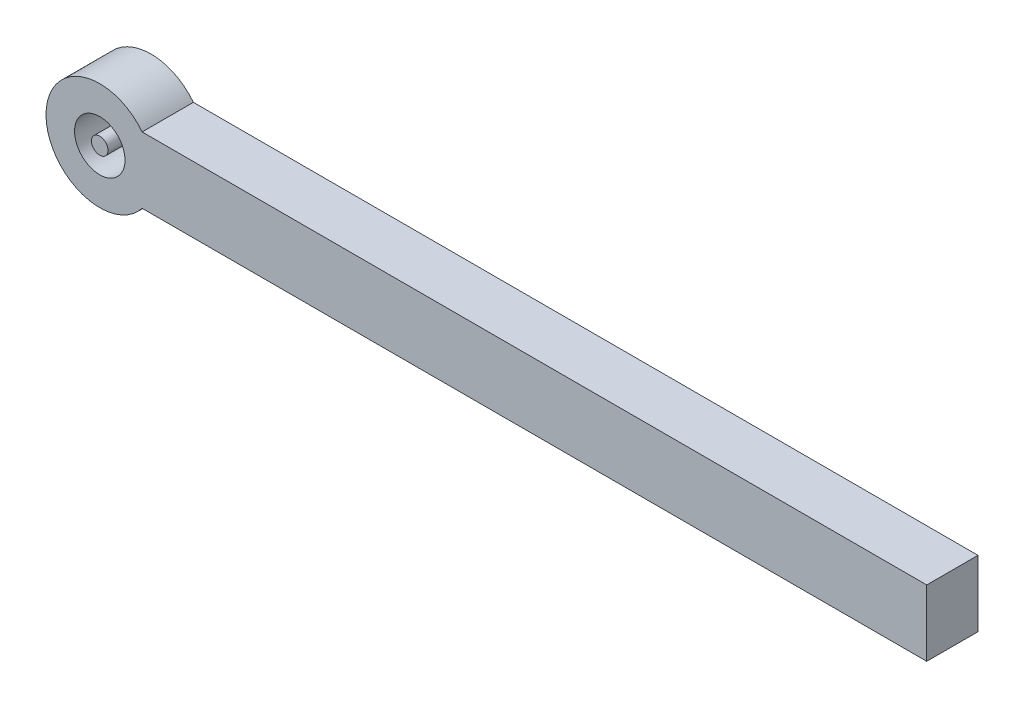
SolidWorks part; units mm, degrees
material "3d打印 35%"
ref_plane "前视基准面" through (0, 0, 0) normal (0, 0, 1) x (1, 0, 0)
ref_plane "上视基准面" through (0, 0, 0) normal (0, 1, 0) x (1, 0, 0)
ref_plane "右视基准面" through (0, 0, 0) normal (1, 0, 0) x (0, 0, -1)
other "Configuration Table"
sketch "草图1" plane through (0, 0, 0) normal (0, 0, 1) x (1, 0, 0)
  line L0 (0, 0) -> (0, 4) construction
  line L1 (0, 0) -> (0, -4) construction
  line L2 (5.1235, 4) -> (100, 4)
  line L3 (100, 4) -> (100, -4)
  line L4 (100, -4) -> (5.1235, -4)
  circle A0 centre (0, 0) radius 1
  circle A1 centre (0, 0) radius 3.05
  arc A2 (5.1235, 4) -> (5.1235, -4) centre (0, 0) ccw
extrude "凸台-拉伸1" add sketch "草图1" along normal blind 4.2 contours L2 A2 L4 L3 A1 | A0 region at (46.6105, 0, 0)
extrude "凸台-拉伸2" add sketch "草图1<4>" against normal blind 2 contours L2 A2 L4 L3 A1 | A1 A0 | A0 region at (46.6105, 0, 0) region at (0, 0, 0) region at (-2.9637, 0, 0)
sketch "草图1<4>" plane through (0, 0, 0) normal (0, 0, 1) x (1, 0, 0) same geometry as "草图1"
